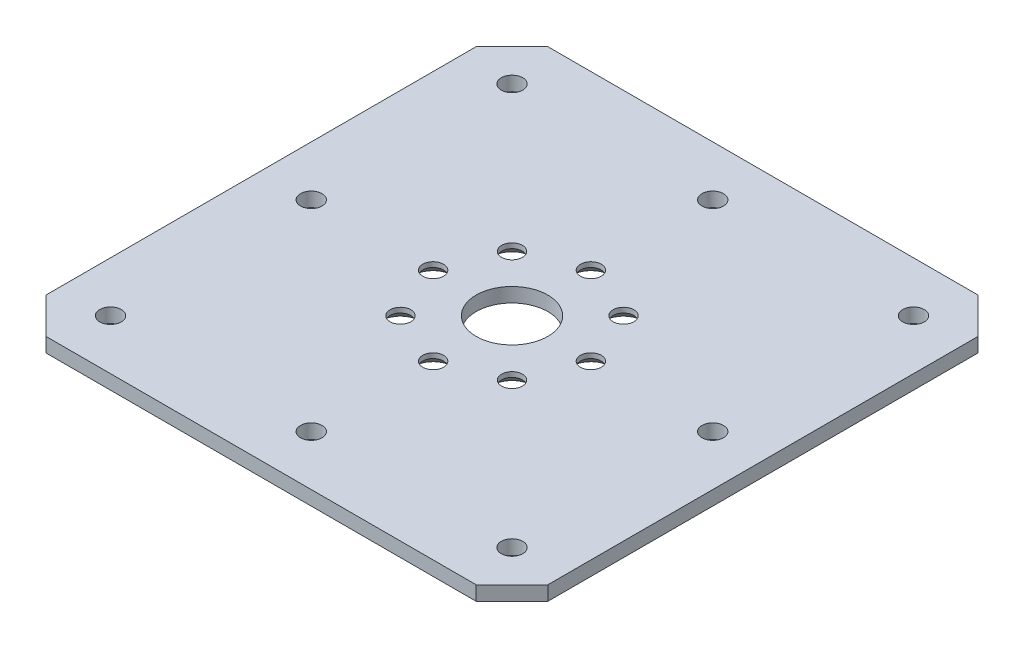
SolidWorks part; units mm, degrees
material "3003 Alloy"
ref_plane "Front Plane" through (0, 0, 0) normal (0, 0, 1) x (1, 0, 0)
ref_plane "Top Plane" through (0, 0, 0) normal (0, 1, 0) x (1, 0, 0)
ref_plane "Right Plane" through (0, 0, 0) normal (1, 0, 0) x (0, 0, -1)
sketch "Sketch1" plane through (0, 0, 0) normal (0, 0, 1) x (1, 0, 0)
  line L0 (-35, 0) -> (35, 0)
  dimension "D1" = 70
sheet metal parameters "Sheet-Metal1" thickness 2 parameters "D1"=3
base flange "Base-Flange1" sketch "Sketch1" end condition blind depth 70 reverse direction no thickness 2 reverse thickness direction no bend radius 3
sketch "Sketch3" plane through (0, 0, 0) normal (0, 1, 0) x (1, 0, 0)
  line L0 (-35, -35) -> (35, -35) construction
  line L1 (-35, -70) -> (-35, 0) construction
  line L2 (35, -70) -> (35, 0) construction
  circle A0 centre (0, -35) radius 5
  dimension "D1" = 10
extrude "Cut-Extrude1" cut sketch "Sketch3" against normal through all normal cut yes
chamfer "Chamfer1" distance 5 angle 45 4 edges at (35, -1, 0) (-35, -1, 0) (35, -1, 70) (-35, -1, 70)
sketch "Sketch4" plane through (0, 0, 0) normal (0, 1, 0) x (1, 0, 0)
  circle A0 centre (11, -35) radius 1.25
  circle A1 centre (-11, -35) radius 1.25
  circle A2 centre (0, -46) radius 1.25
  circle A3 centre (0, -24) radius 1.25
  circle A4 centre (7.7782, -42.7782) radius 1.25
  circle A5 centre (7.7782, -27.2218) radius 1.25
  circle A6 centre (-7.7782, -27.2218) radius 1.25
  circle A7 centre (-7.7782, -42.7782) radius 1.25
  dimension "D1" = 2.5
extrude "Cut-Extrude2" cut sketch "Sketch4" against normal through all normal cut yes
hole_wizard "CSK for M2.5 Countersunk Raised Head Screw1" positions "3DSketch1" profile "Sketch5" countersink size "M2.5" standard "DIN" end condition through all
sketch3d "3DSketch1"
  line L0 (0, -2, 46) -> (0, 0, 46) construction
  line L1 (-7.7782, -2, 42.7782) -> (-7.7782, 0, 42.7782) construction
  line L2 (-11, -2, 35) -> (-11, 0, 35) construction
  line L3 (-7.7782, -2, 27.2218) -> (-7.7782, 0, 27.2218) construction
  line L4 (0, -2, 24) -> (0, 0, 24) construction
  line L5 (7.7782, -2, 27.2218) -> (7.7782, 0, 27.2218) construction
  line L6 (11, -2, 35) -> (11, 0, 35) construction
  line L7 (7.7782, -2, 42.7782) -> (7.7782, 0, 42.7782) construction
  point P0 (0, -2, 46)
  point P4 (-7.7782, -2, 42.7782)
  point P8 (-11, -2, 35)
  point P12 (-7.7782, -2, 27.2218)
  point P16 (0, -2, 24)
  point P20 (7.7782, -2, 27.2218)
  point P24 (11, -2, 35)
  point P28 (7.7782, -2, 42.7782)
sketch "Sketch5" plane through (0, -2, 46) normal (1, 0, 0) x (0, 0, -1)
  line L0 (0, 0) -> (0, 2)
  line L1 (0, 2) -> (1.45, 2)
  line L2 (1.45, 2) -> (1.45, 1.3)
  line L3 (1.45, 1.3) -> (2.75, 0)
  line L5 (2.75, 0) -> (0, 0)
  line L6 (-1.45, 1.3) -> (-2.75, 0) construction
  line L11 (0, -6.35) -> (0, 107.95) construction
  dimension "Thru Hole Dia." = 2.9
  dimension "Thru Hole Depth" = 2
  dimension "Near C'Sink Dia." = 5.5
  dimension "Near C'Sink Angle" = 90
sketch "Sketch6" plane through (0, 0, 0) normal (0, 1, 0) x (1, 0, 0)
  line L0 (-35, -65) -> (-35, -5) construction
  line L1 (28, -63) -> (-28, -63) construction
  line L2 (28, -63) -> (28, -7) construction
  line L3 (28, -7) -> (-28, -7) construction
  line L4 (-28, -63) -> (-28, -7) construction
  line L5 (28, -63) -> (-28, -7) construction
  line L6 (28, -7) -> (-28, -63) construction
  line L7 (-30, 0) -> (30, 0) construction
  circle A0 centre (-28, -7) radius 1.5
  circle A1 centre (0, -7) radius 1.5
  circle A2 centre (28, -7) radius 1.5
  circle A3 centre (28, -35) radius 1.5
  circle A4 centre (28, -63) radius 1.5
  circle A5 centre (0, -63) radius 1.5
  circle A6 centre (-28, -63) radius 1.5
  circle A7 centre (-28, -35) radius 1.5
  point P0 (0, -35)
  dimension "D3" = 3
  dimension "D1" = 7
  dimension "D2" = 7
extrude "Cut-Extrude3" cut sketch "Sketch6" against normal through all normal cut yes
flat pattern "Flat-Pattern1" [suppressed]
sketch "Bend-Lines1" plane through (0, 0, 0) normal (0, 1, 0) x (-1, 0, 0)
